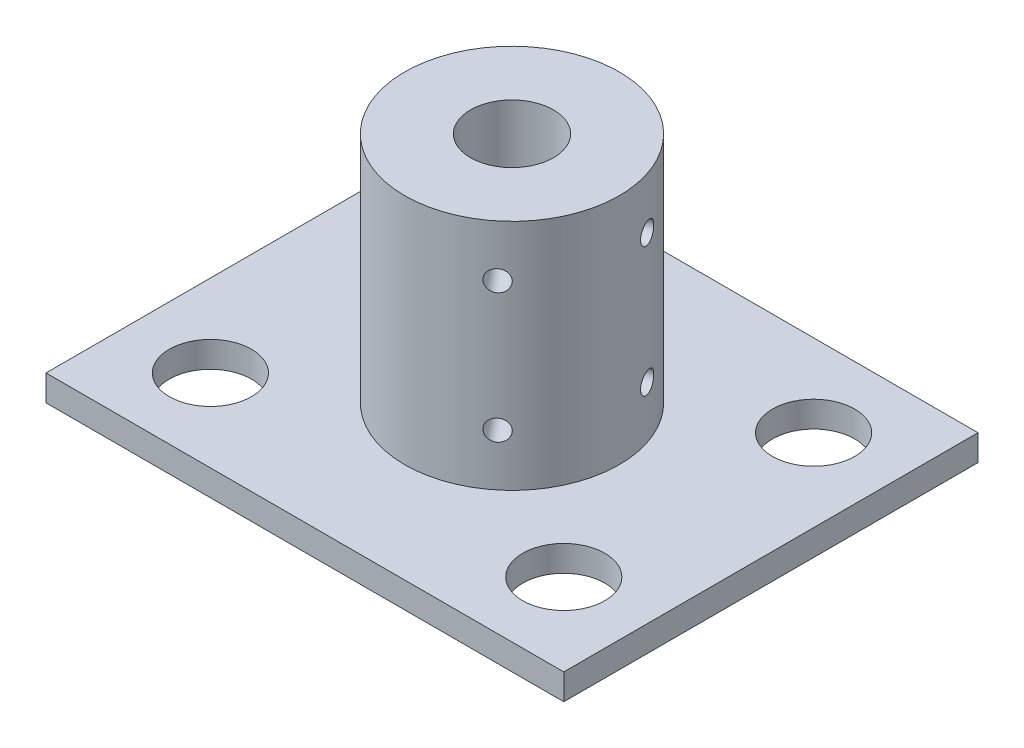
SolidWorks part; units mm, degrees
ref_plane "Front Plane" through (0, 0, 0) normal (0, 0, 1) x (1, 0, 0)
ref_plane "Top Plane" through (0, 0, 0) normal (0, 1, 0) x (1, 0, 0)
ref_plane "Right Plane" through (0, 0, 0) normal (1, 0, 0) x (0, 0, -1)
sketch "Sketch1" plane through (0, 0, 0) normal (0, 1, 0) x (1, 0, 0)
  line L1 (0, 0) -> (100, 0)
  line L2 (0, 0) -> (0, -80)
  line L3 (0, -80) -> (100, -80)
  line L4 (100, 0) -> (100, -80)
  dimension "D1" = 80
  dimension "D2" = 100
extrude "Boss-Extrude1" add sketch "Sketch1" along normal blind 5
sketch "Sketch2" plane through (0, 5, 0) normal (0, 1, 0) x (1, 0, 0)
  line L0 (0, 0) -> (0, -80) construction
  line L1 (0, -80) -> (100, -80) construction
  circle A0 centre (50, -40) radius 8.0125
  dimension "D1" = 16.025
  dimension "D2" = 50
  dimension "D3" = 40
extrude "Cut-Extrude1" cut sketch "Sketch2" against normal through all
sketch "Sketch3" plane through (0, 5, 0) normal (0, 1, 0) x (1, 0, 0)
  circle A0 centre (50, -40) radius 8.0125
  circle A1 centre (50, -40) radius 20.715
  dimension "D1" = 16.025
  dimension "D2" = 41.43
extrude "Boss-Extrude2" add sketch "Sketch3" along normal blind 45
ref_point "Point1" parameters "D1"=14.287
ref_plane "Plane1" through (63.181, 50, 55.9804) normal (0.6363, 0, 0.7714) x (0.7714, 0, -0.6363)
sketch "Sketch4" plane through (63.181, 50, 55.9804) normal (0.6363, 0, 0.7714) x (0.7714, 0, -0.6363)
  line L0 (20.715, 0) -> (-20.715, 0) construction
  line L1 (20.715, -45) -> (-20.715, -45) construction
  circle A0 centre (0, -10) radius 2.0193
  circle A1 centre (0, -35) radius 2.0193
  point P4 (0, 0)
  dimension "D1" = 4.0386
  dimension "D2" = 4.0386
  dimension "D3" = 10
  dimension "D4" = 10
extrude "Cut-Extrude2" cut sketch "Sketch4" against normal blind 15
ref_plane "Plane2" through (52.5543, 0, -17.6013) normal (0.9482, 0, -0.3176) x (0, -1, 0)
ref_axis "Axis1" through (50, 0, 40) along (0, 1, 0)
ref_plane "Plane3" through (17.0883, 0, 51.0227) normal (-0.3176, 0, -0.9482) x (0, 1, 0)
sketch "Sketch6" plane through (52.5543, 0, -17.6013) normal (0.9482, 0, -0.3176) x (0, -1, 0)
  line L0 (27.5, -53.8082) -> (-27.5, -53.8082) construction
  line L1 (-50, -33.0932) -> (-50, -74.5232) construction
  line L2 (-5, -33.0932) -> (-5, -74.5232) construction
  circle A0 centre (-40, -53.8082) radius 2.0193
  circle A1 centre (-15, -53.8082) radius 2.0193
  point P4 (0, 0)
  point P7 (0, 0)
  dimension "D1" = 4.0386
  dimension "D2" = 4.0386
  dimension "D3" = 10
  dimension "D4" = 10
extrude "Cut-Extrude3" cut sketch "Sketch6" against normal blind 15
sketch "Sketch7" plane through (0, 5, 0) normal (0, 1, 0) x (1, 0, 0)
  line L0 (0, -80) -> (100, -80) construction
  line L1 (0, 0) -> (0, -80) construction
  line L2 (100, 0) -> (0, 0) construction
  line L3 (100, -80) -> (100, 0) construction
  circle A0 centre (84.125, -64.125) radius 7.9375
  circle A1 centre (15.875, -64.125) radius 7.9375
  circle A2 centre (15.875, -15.875) radius 7.9375
  circle A3 centre (84.125, -15.875) radius 7.9375
  point P8 (13.2997, -64.367)
  point P9 (15.9404, -63.6595)
  point P10 (0, 0)
  point P15 (0, 0)
  point P16 (0, 0)
  point P17 (0, 0)
  point P18 (0, 0)
  point P19 (15.875, -17.6145)
  dimension "D1" = 15.875
  dimension "D2" = 15.875
  dimension "D3" = 15.875
  dimension "D4" = 15.875
  dimension "D8" = 15.875
  dimension "D5" = 15.875
  dimension "D6" = 15.875
  dimension "D7" = 15.875
extrude "Cut-Extrude4" cut sketch "Sketch7" against normal through all
